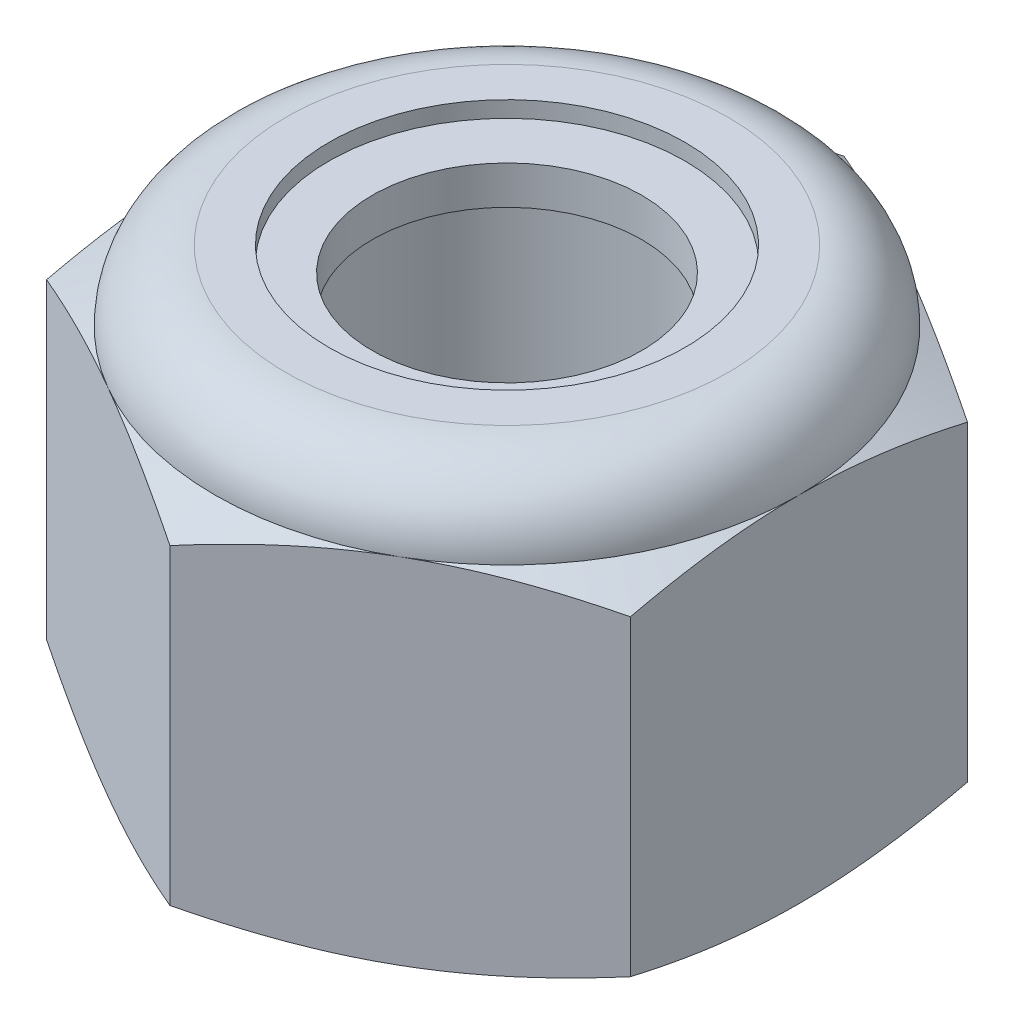
SolidWorks part; units mm, degrees
ref_plane "Front" through (0, 0, 0) normal (0, 0, 1) x (1, 0, 0)
ref_plane "Top" through (0, 0, 0) normal (0, 1, 0) x (1, 0, 0)
ref_plane "Right" through (0, 0, 0) normal (1, 0, 0) x (0, 0, -1)
sketch "Sketch1" plane through (0, 0, 0) normal (0, 1, 0) x (1, 0, 0)
  line L1 (0, 3.1754) -> (-2.75, 1.5877)
  line L2 (-2.75, 1.5877) -> (-2.75, -1.5877)
  line L3 (-2.75, -1.5877) -> (0, -3.1754)
  line L4 (0, -3.1754) -> (2.75, -1.5877)
  line L5 (2.75, -1.5877) -> (2.75, 1.5877)
  line L6 (2.75, 1.5877) -> (0, 3.1754)
  circle A0 centre (0, 0) radius 2.75 construction
  dimension "Hex Flats" = 5.5
extrude "Extrude1" add sketch "Sketch1" along normal blind 4
sketch "Sketch2" plane through (0, 0, 0) normal (1, 0, 0) x (0, 0, -1)
  line L0 (-1.5, 0) -> (-1.5, 4) construction
  line L1 (0, 0) -> (1.5, 0)
  line L2 (0, 0) -> (0, 4)
  line L3 (0, 4) -> (1.5, 4)
  line L4 (1.5, 0) -> (1.5, 4)
  line L5 (-1.5877, 4) -> (1.5877, 4) construction
  line L7 (0, -1.5) -> (0, 0) construction
  dimension "Thread Dia" = 3
revolve "Revolve1" add sketch "Sketch2" angle 360 about L7
sketch "Sketch3" plane through (0, 0, 0) normal (1, 0, 0) x (0, 0, -1)
  line L0 (1.5, 4) -> (-1.5, 4) construction
  line L1 (-1.5, 4) -> (-1.5, 3.5) construction
  line L2 (-1.5, 3.5) -> (1.5, 4) construction
  line L3 (1.5, 4) -> (1.5103, 3.9384) construction
  line L4 (1.5103, 3.9384) -> (1.5822, 3.5068)
  line L5 (1.5822, 3.5068) -> (1.2896, 3.6164)
  line L6 (1.2896, 3.6164) -> (1.269, 3.7397)
  line L7 (1.269, 3.7397) -> (1.5103, 3.9384)
  line L8 (1.2793, 3.6781) -> (1.5462, 3.7226) construction
  line L9 (1.5, 4) -> (1.5, 3.7149) construction
  line L10 (1.5, 3.7149) -> (-1.5, 3.2149) construction
  line L11 (-1.5, 3.2149) -> (-1.5, 3.5) construction
  line L12 (-0.0892, 4) -> (0.0892, 2.9297) construction
  line L13 (-1.5, 0) -> (-1.5, 4) construction
  line L14 (0, 4) -> (1.5, 4) construction
  line L15 (1.5, 0) -> (1.5, 4) construction
  point P13 (0, 3.4649)
  dimension "D1" = 0.0625
  dimension "D2" = 0.125
  dimension "D4" = 60
  dimension "D5" = 0.5
revolve "Cut-Revolve1" [suppressed] cut sketch "Sketch3" angle 360 about L12
pattern_linear "LPattern1" [suppressed] count 8 spacing 0.5 along (0, -1, 0) count 2 spacing 0.5 along (0, 1, 0) of bodies 110
sketch "Sketch4" plane through (0, 0, 0) normal (1, 0, 0) x (0, 0, -1)
  line L0 (0, 4) -> (1.5, 4)
  line L1 (1.5, 4) -> (1.269, 3.8923)
  line L2 (1.269, 3.8923) -> (1.269, 0.1077)
  line L3 (1.269, 0.1077) -> (1.5, 0)
  line L4 (1.5, 0) -> (0, 0)
  line L5 (0, 0) -> (0, 4)
  line L6 (1.5, 0) -> (1.5, 4) construction
  line L7 (0, 4) -> (1.5, 4) construction
  line L8 (0, 0) -> (1.5, 0) construction
  line L9 (0, 0) -> (0, 4) construction
  line L10 (0, 4) -> (0, 4.2549) construction
  dimension "D1" = 25
revolve "Cut-Revolve2" cut sketch "Sketch4" angle 360 about L10
combine bodies "Combine1" operation type subtract main body 112 bodies to subtract 109
sketch "Sketch5" plane through (0, 0, 0) normal (1, 0, 0) x (0, 0, -1)
  line L0 (0, 0) -> (2.75, 0)
  line L1 (2.75, 0) -> (3.1754, 0.1984)
  line L2 (3.1754, 0.1984) -> (3.1754, 3.135)
  line L3 (3.1754, 3.135) -> (2.75, 3.3333)
  line L4 (2.0833, 4) -> (2.0833, 5.27)
  line L5 (2.0833, 5.27) -> (4.4454, 5.27)
  line L6 (4.4454, 5.27) -> (4.4454, -1.27)
  line L7 (4.4454, -1.27) -> (0, -1.27)
  line L8 (0, -1.27) -> (0, 0)
  line L9 (2.75, 3.3333) -> (2.75, 0) construction
  line L10 (0, 0) -> (1.5, 0) construction
  line L13 (3.1754, 1.6667) -> (4.4454, 1.6667) construction
  line L14 (3.1754, 4) -> (3.1754, 0) construction
  line L15 (0, 0) -> (0, 5.27) construction
  line L20 (0, 5.27) -> (2.0833, 5.27) construction
  line L22 (0, 4) -> (1.5, 4) construction
  arc A0 (2.75, 3.3333) -> (2.0833, 4) centre (2.0833, 3.3333) ccw
  dimension "D1" = 25
  dimension "D2" = 1.27
  dimension "D3" = 4
  dimension "D4" = 0.6667
revolve "Cut-Revolve3" cut sketch "Sketch5" angle 360 about L15
sketch "Sketch6" plane through (0, 0, 0) normal (1, 0, 0) x (0, 0, -1)
  line L0 (0, 3.3333) -> (2.5976, 3.3333)
  line L1 (2.0833, 3.8476) -> (1.6762, 3.8476)
  line L2 (0, 5.27) -> (0, 3.3333)
  line L3 (1.6762, 5.27) -> (0, 5.27)
  line L4 (0, 5.27) -> (2.0833, 5.27) construction
  line L5 (0, 0) -> (0, 5.27) construction
  line L6 (0, 5.27) -> (0, 44.323) construction
  line L7 (1.6762, 3.8476) -> (1.6762, 5.27)
  line L8 (2.0833, 4) -> (2.0833, 3.8476) construction
  line L9 (1.6762, 3.8476) -> (1.269, 3.8476) construction
  line L10 (1.269, 3.8476) -> (1.269, 3.8923) construction
  arc A0 (2.5976, 3.3333) -> (2.0833, 3.8476) centre (2.0833, 3.3333) ccw
  arc A1 (2.75, 3.3333) -> (2.0833, 4) centre (2.0833, 3.3333) ccw construction
  dimension "D1" = 0.1524
revolve "Cut-Revolve4" cut sketch "Sketch6" angle 360 about L6
sketch "Sketch7" plane through (0, 0, 0) normal (1, 0, 0) x (0, 0, -1)
  line L0 (1.269, 3.4095) -> (2.5147, 3.4095)
  line L1 (2.0833, 3.7714) -> (1.269, 3.7714)
  line L2 (1.269, 3.7714) -> (1.269, 3.4095)
  line L3 (1.269, 3.4095) -> (0, 3.4095) construction
  line L4 (0, 3.4095) -> (0, 3.7714) construction
  line L5 (0, 3.7714) -> (1.269, 3.7714) construction
  line L6 (1.269, 3.4095) -> (1.269, 3.3333) construction
  line L7 (0, 3.3333) -> (2.5976, 3.3333) construction
  line L8 (2.0833, 3.7714) -> (2.0833, 3.8476) construction
  arc A0 (2.5147, 3.4095) -> (2.0833, 3.7714) centre (2.0833, 3.3333) ccw
  arc A2 (2.5976, 3.3333) -> (2.0833, 3.8476) centre (2.0833, 3.3333) ccw construction
  dimension "D1" = 0.0762
revolve "Revolve2" add sketch "Sketch7" angle 360 about L4
equation "\"D1@Sketch3\"=\"Thread Pitch@Sketch3\"/8"
equation "\"D2@Sketch3\"=\"Thread Pitch@Sketch3\"/4"
equation "\"D5@Sketch3\"=\"Thread Pitch@Sketch3\""
equation "\"D4@LPattern1\"=\"Thread Pitch@Sketch3\""
equation "\"D3@LPattern1\"=\"Thread Pitch@Sketch3\""
equation "\"D1@LPattern1\"=\"Height@Extrude1\"/\"Thread Pitch@Sketch3\""
equation "\"D4@Sketch5\"=\"Height@Extrude1\"/6"
